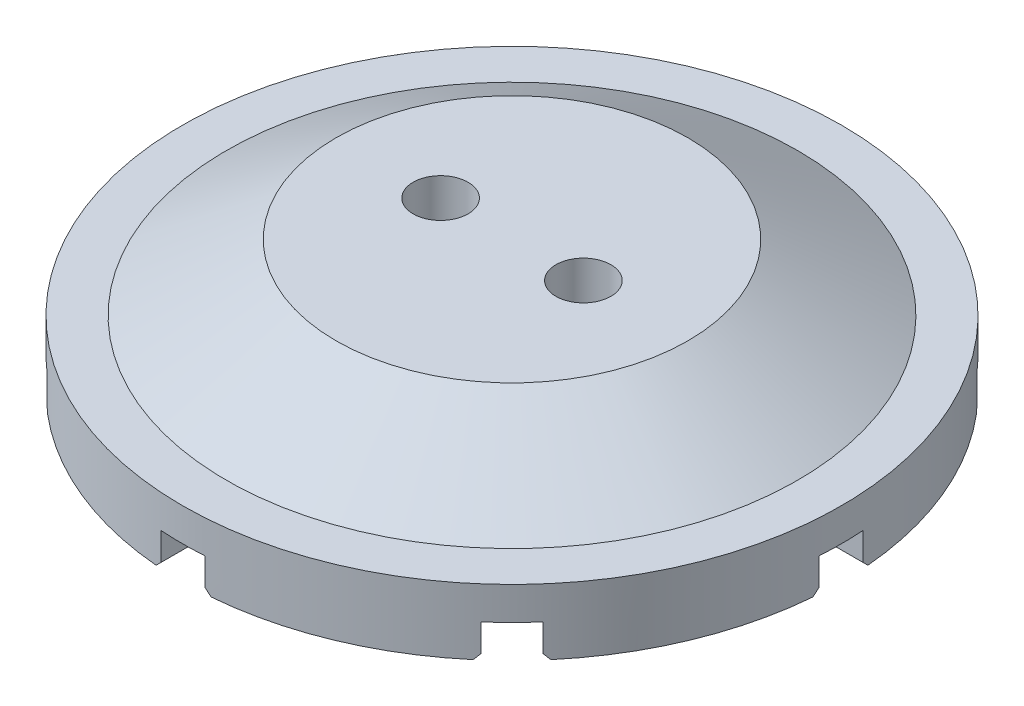
SolidWorks part; units mm, degrees
ref_plane "Front Plane" through (0, 0, 0) normal (0, 0, 1) x (1, 0, 0)
ref_plane "Top Plane" through (0, 0, 0) normal (0, 1, 0) x (1, 0, 0)
ref_plane "Right Plane" through (0, 0, 0) normal (1, 0, 0) x (0, 0, -1)
sketch "Sketch1" plane through (0, 0, 0) normal (0, 1, 0) x (1, 0, 0)
  circle A0 centre (0, 0) radius 8
  dimension "D1" = 16
extrude "Boss-Extrude1" add sketch "Sketch1" along normal blind 3
sketch "Sketch2" plane through (0, 3, 0) normal (0, 1, 0) x (1, 0, 0)
  line L0 (-3.25, 0) -> (3.25, 0) construction
  circle A0 centre (-3.25, 0) radius 1.25
  circle A1 centre (3.25, 0) radius 1.25
  point P4 (0, 0)
  dimension "D2" = 2.5
  dimension "D1" = 6.5
extrude "Cut-Extrude1" cut sketch "Sketch2" against normal through all
sketch "Sketch3" plane through (0, 0, 0) normal (0, -1, 0) x (1, 0, 0)
  circle A0 centre (0, 0) radius 15
  dimension "D1" = 30
extrude "Boss-Extrude2" add sketch "Sketch3" along normal blind 3
chamfer "Chamfer1" distance 5 angle 31 1 edges at (0, 0, 8) first distance on face at (0, 0, 8)
sketch "Sketch4" plane through (0, -3, 0) normal (0, -1, 0) x (1, 0, 0)
  line L0 (0, 0) -> (15, 0) construction
  line L2 (15, 1) -> (0, 1)
  line L3 (15, 1) -> (15, -1)
  line L4 (15, -1) -> (0, -1)
  line L5 (0, 1) -> (0, -1)
  line L6 (15, 1) -> (0, -1) construction
  line L7 (15, -1) -> (0, 1) construction
  circle A0 centre (0, 0) radius 15 construction
  point P5 (7.5, 0)
  dimension "D1" = 2
extrude "Cut-Extrude2" cut sketch "Sketch4" against normal blind 1.5
chamfer "Chamfer2" distance 0.25 angle 45 2 edges at (7.4833, -3, -1) (7.4833, -3, 1)
pattern_circular "CirPattern1" count 8 over 360 about axis through (0, -3, 0) along (0, -1, 0) of "Cut-Extrude2", "Chamfer2"
fillet "Fillet1" radius 0.5 8 edges at (1, -2.125, -2.4142) (-1, -2.125, -2.4142) (-2.4142, -2.125, -1) (-2.4142, -2.125, 1) (-1, -2.125, 2.4142) (1, -2.125, 2.4142) (2.4142, -2.125, -1) (2.4142, -2.125, 1)
